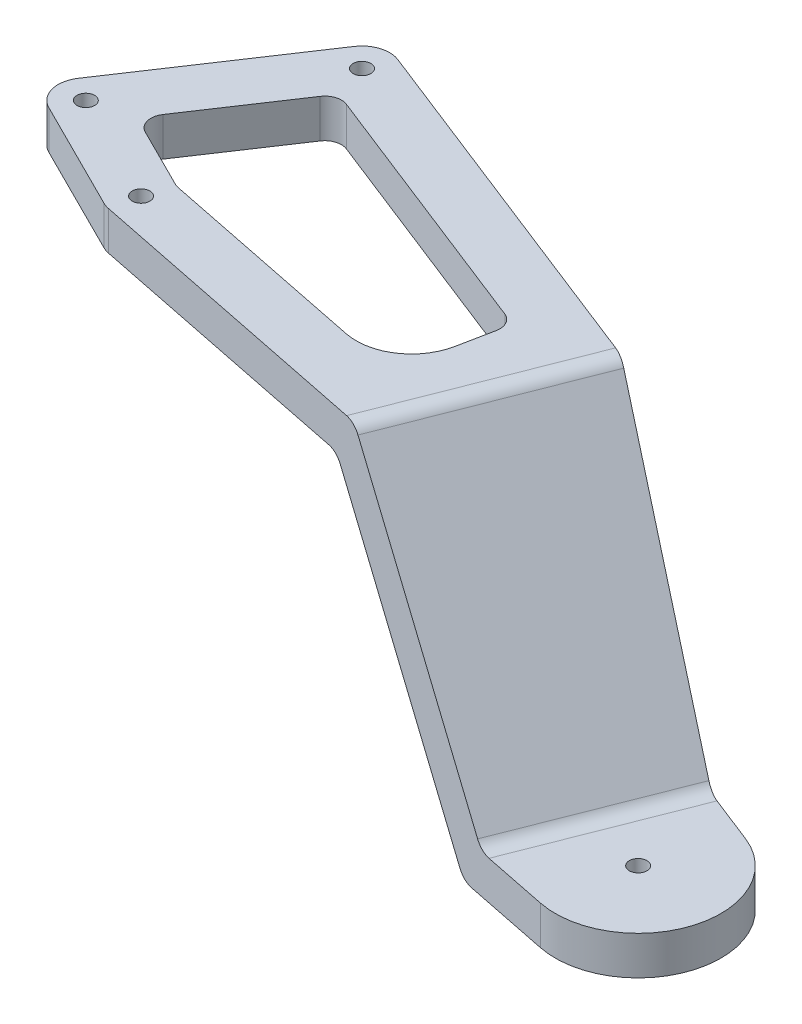
SolidWorks part; units mm, degrees
material "ABS"
ref_plane "Front Plane" through (0, 0, 0) normal (0, 0, 1) x (1, 0, 0)
ref_plane "Top Plane" through (0, 0, 0) normal (0, 1, 0) x (1, 0, 0)
ref_plane "Right Plane" through (0, 0, 0) normal (1, 0, 0) x (0, 0, -1)
sketch "Sketch1" plane through (0, 0, 0) normal (0, 1, 0) x (1, 0, 0)
  line L1 (1.8271, 44.6542) -> (105.4813, 3.9626)
  line L2 (97.0297, -24.703) -> (-0.9901, -4.901)
  line L4 (-4.1603, 42.7735) -> (-24.1603, 12.7735)
  line L5 (-22.2361, 5.5279) -> (-2.2361, -4.4721)
  arc A0 (-4.1603, 42.7735) -> (1.8271, 44.6542) centre (0, 40) cw
  arc A1 (105.4813, 3.9626) -> (97.0297, -24.703) centre (100, -10) cw
  arc A2 (-0.9901, -4.901) -> (-2.2361, -4.4721) centre (0, 0) cw
  arc A3 (-24.1603, 12.7735) -> (-22.2361, 5.5279) centre (-20, 10) ccw
  dimension "D1" = 5
  dimension "D2" = 5
  dimension "D3" = 15
  dimension "D9" = 5
  dimension "D4" = 10
  dimension "D5" = 40
  dimension "D6" = 100
  dimension "D7" = 20
  dimension "D8" = 30
extrude "Boss-Extrude1" add sketch "Sketch1" along normal blind 17
sketch "Sketch2" plane through (0, 17, 0) normal (0, 1, 0) x (1, 0, 0)
  circle A0 centre (0, 40) radius 1.6
  circle A1 centre (0, 0) radius 1.6
  circle A2 centre (100, -10) radius 1.6
  circle A3 centre (-20, 10) radius 1.6
  arc A4 (-24.1603, 12.7735) -> (-22.2361, 5.5279) centre (-20, 10) ccw construction
  dimension "D1" = 3.2
  dimension "D2" = 3.2
extrude "Cut-Extrude1" cut sketch "Sketch2" against normal through all
sketch "Sketch3" plane through (0, 17, 0) normal (0, 1, 0) x (1, 0, 0)
  line L4 (-0.9901, -4.901) -> (97.0297, -24.703)
  line L5 (105.4813, 3.9626) -> (1.8271, 44.6542)
  line L6 (-4.1603, 42.7735) -> (-24.1603, 12.7735)
  line L7 (-22.2361, 5.5279) -> (-2.2361, -4.4721)
  line L8 (-0.9901, -4.901) -> (97.0297, -24.703)
  line L9 (105.4813, 3.9626) -> (1.8271, 44.6542)
  line L10 (-4.1603, 42.7735) -> (-24.1603, 12.7735)
  line L11 (-22.2361, 5.5279) -> (-2.2361, -4.4721)
  arc A4 (-2.2361, -4.4721) -> (-0.9901, -4.901) centre (0, 0) ccw
  arc A5 (97.0297, -24.703) -> (105.4813, 3.9626) centre (100, -10) ccw
  arc A6 (1.8271, 44.6542) -> (-4.1603, 42.7735) centre (0, 40) ccw
  arc A7 (-24.1603, 12.7735) -> (-22.2361, 5.5279) centre (-20, 10) ccw
  arc A8 (-2.2361, -4.4721) -> (-0.9901, -4.901) centre (0, 0) ccw
  arc A9 (97.0297, -24.703) -> (105.4813, 3.9626) centre (100, -10) ccw
  arc A10 (1.8271, 44.6542) -> (-4.1603, 42.7735) centre (0, 40) ccw
  arc A11 (-24.1603, 12.7735) -> (-22.2361, 5.5279) centre (-20, 10) ccw
  dimension "D1" = 0
extrude "Boss-Extrude2" add sketch "Sketch3" along normal blind 40
sketch "Sketch10" plane through (0, 57, 0) normal (0, 1, 0) x (1, 0, 0)
  line L4 (53.7435, 13.5304) -> (50, -5)
  line L12 (1.6416, 4.7694) -> (50, -5)
  line L13 (53.7435, 13.5304) -> (1.9246, 33.873)
  line L14 (1.9246, 33.873) -> (-12.698, 11.9392)
  line L15 (-12.698, 11.9392) -> (1.6416, 4.7694)
  dimension "D2" = 64.8107
extrude "Cut-Extrude8" cut sketch "Sketch10" against normal through all both
fillet "Fillet3" radius 3 4 edges at (53.7435, 28.5, -13.5304) (1.6416, 28.5, -4.7694) (-12.698, 28.5, -11.9392) (1.9246, 28.5, -33.873)
fillet "Fillet4" radius 10 1 edges at (50, 28.5, 5)
sketch "Sketch4" plane through (0, 0, 0) normal (0, -1, 0) x (1, 0, 0)
  circle A0 centre (100, 10) radius 1.6 construction
  circle A1 centre (0, -40) radius 1.6 construction
  circle A2 centre (-20, -10) radius 1.6 construction
  circle A3 centre (0, 0) radius 1.6 construction
  circle A4 centre (100, 10) radius 1.6
  circle A5 centre (0, -40) radius 1.6
  circle A6 centre (-20, -10) radius 1.6
  circle A7 centre (0, 0) radius 1.6
extrude "Cut-Extrude2" cut sketch "Sketch4" against normal through all
sketch "Sketch5" plane through (15.4331, 0, -39.3129) normal (0.3654, 0, -0.9308) x (-0.9308, 0, -0.3654)
  line L0 (27.1571, 50) -> (-52.8429, 50)
  line L1 (27.1571, 57) -> (27.1571, 0) construction
  line L2 (-52.8429, 50) -> (-81.8429, 0)
  line L3 (-96.7384, 0) -> (14.6168, 0) construction
  line L4 (-81.8429, 0) -> (28.1571, 0)
  line L5 (28.1571, 0) -> (28.1571, 50)
  line L6 (28.1571, 50) -> (27.1571, 50)
  line L7 (-96.7384, 57) -> (14.6168, 57) construction
  dimension "D1" = 7
  dimension "D2" = 80
  dimension "D3" = 1
  dimension "D4" = 110
extrude "Cut-Extrude3" cut sketch "Sketch5" against normal through all
sketch "Sketch6" plane through (15.4331, 0, -39.3129) normal (0.3654, 0, -0.9308) x (-0.9308, 0, -0.3654)
  line L0 (-111.7384, 7) -> (-85.8751, 7)
  line L1 (-111.7384, 57) -> (-111.7384, 0) construction
  line L2 (-85.8751, 7) -> (-56.8751, 57)
  line L3 (-96.7384, 57) -> (14.6168, 57) construction
  line L4 (-56.8751, 57) -> (-112.7384, 57)
  line L5 (-112.7384, 57) -> (-112.7384, 7)
  line L6 (-112.7384, 7) -> (-111.7384, 7)
  line L7 (-96.7384, 0) -> (-81.8429, 0) construction
  line L8 (-52.8429, 50) -> (-81.8429, 0) construction
  dimension "D1" = 7
  dimension "D2" = 1
  dimension "D4" = 7
extrude "Cut-Extrude4" cut sketch "Sketch6" against normal through all
sketch "Sketch7" [suppressed] plane through (15.4331, 0, -39.3129) normal (0.3654, 0, -0.9308) x (-0.9308, 0, -0.3654)
  line L0 (27.1571, 7) -> (-52.8429, 7)
  line L1 (27.1571, 57) -> (27.1571, 0) construction
  line L2 (-52.8429, 7) -> (-81.8429, 57)
  line L3 (-96.7384, 57) -> (14.6168, 57) construction
  line L4 (-81.8429, 57) -> (28.1571, 57)
  line L5 (28.1571, 57) -> (28.1571, 7)
  line L6 (28.1571, 7) -> (27.1571, 7)
  line L7 (-96.7384, 0) -> (14.6168, 0) construction
  dimension "D1" = 1
  dimension "D2" = 110
  dimension "D3" = 7
  dimension "D4" = 80
extrude "Cut-Extrude5" [suppressed] cut sketch "Sketch7" against normal through all
sketch "Sketch8" [suppressed] plane through (15.4331, 0, -39.3129) normal (0.3654, 0, -0.9308) x (-0.9308, 0, -0.3654)
  line L0 (-56.8751, 0) -> (-85.8751, 50)
  line L1 (-96.7384, 0) -> (14.6168, 0) construction
  line L2 (-85.8751, 50) -> (-111.7384, 50)
  line L3 (-111.7384, 57) -> (-111.7384, 0) construction
  line L4 (-111.7384, 50) -> (-112.7384, 50)
  line L5 (-112.7384, 50) -> (-112.7384, 0)
  line L6 (-112.7384, 0) -> (-56.8751, 0)
  line L7 (-96.7384, 57) -> (-81.8429, 57) construction
  line L8 (-81.8429, 57) -> (-52.8429, 7) construction
  dimension "D1" = 7
  dimension "D2" = 1
  dimension "D4" = 7
extrude "Cut-Extrude6" [suppressed] cut sketch "Sketch8" against normal through all
fillet "Fillet1" [suppressed] radius 3
fillet "Fillet2" radius 3 4 edges at (85.6117, 0, 5.8888) (57.6818, 50, -2.3255) (61.5652, 57, -1.1834) (89.4951, 7, 7.0309)
